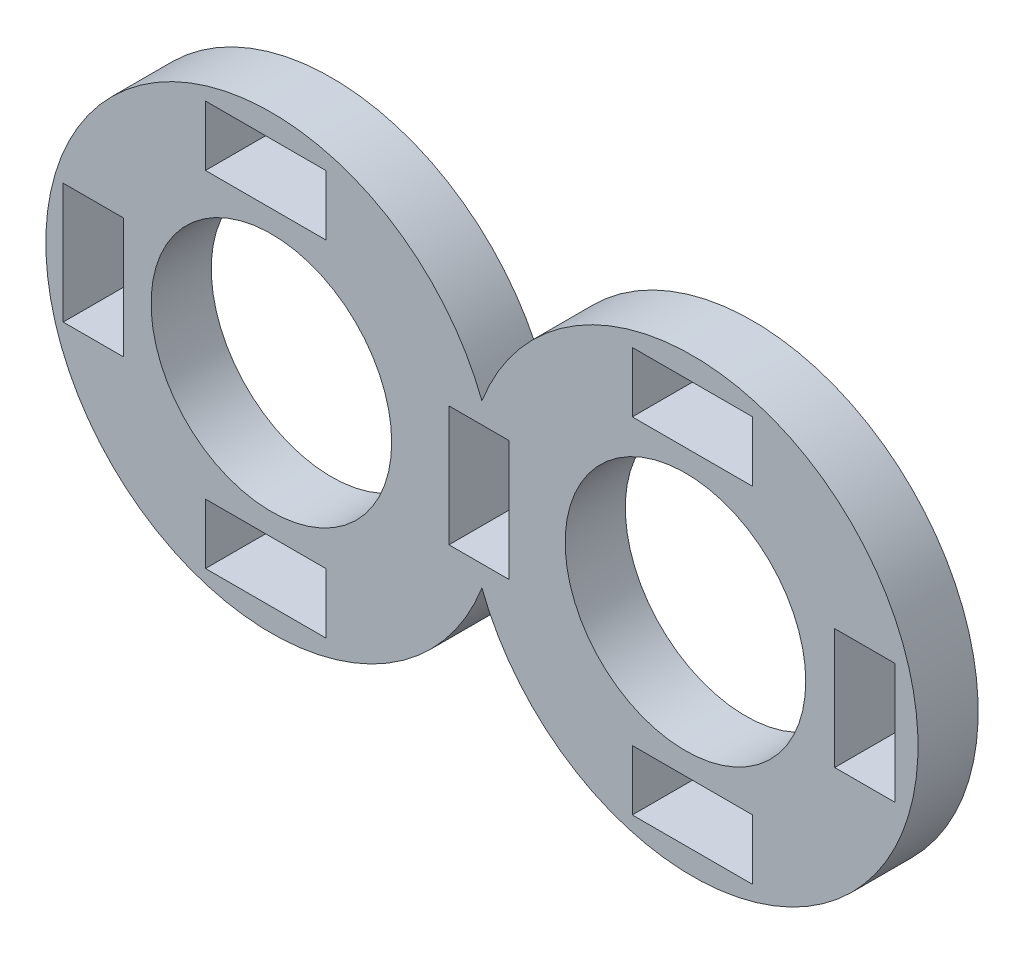
SolidWorks part; units mm, degrees
ref_plane "Front Plane" through (0, 0, 0) normal (0, 0, 1) x (1, 0, 0)
ref_plane "Top Plane" through (0, 0, 0) normal (0, 1, 0) x (1, 0, 0)
ref_plane "Right Plane" through (0, 0, 0) normal (1, 0, 0) x (0, 0, -1)
sketch "Sketch1" plane through (0, 0, 0) normal (0, 0, 1) x (1, 0, 0)
  line L0 (7, 0) -> (0, 0) construction
  circle A0 centre (0, 0) radius 3.75
  circle A1 centre (7, 0) radius 3.75
  circle A2 centre (0, 0) radius 2
  circle A3 centre (7, 0) radius 2
extrude "Boss-Extrude1" add sketch "Sketch1" along normal blind 1 contours A0 | A1
sketch "Sketch2" plane through (0, 0, 0) normal (0, 0, 1) x (1, 0, 0)
  circle A0 centre (0, 0) radius 2
  circle A1 centre (6.8835, 0) radius 2
  point P4 (0, 0)
extrude "Cut-Extrude3" cut sketch "Sketch2" along normal blind 1 from surface starting at face at (3.5, 0, 0)
sketch "Sketch3" plane through (0, 0, 0) normal (0, 0, 1) x (1, 0, 0)
  line L5 (6, -2.3653) -> (8, -2.3653)
  line L6 (9.3653, -1) -> (10.3653, -1)
  line L7 (9.3653, -1) -> (9.3653, 1)
  line L8 (9.3653, 1) -> (10.3653, 1)
  line L9 (10.3653, -1) -> (10.3653, 1)
  line L12 (6, -2.3653) -> (6, -3.3653)
  line L13 (6, -3.3653) -> (8, -3.3653)
  line L14 (8, -2.3653) -> (8, -3.3653)
  line L15 (8, 2.3653) -> (6, 2.3653)
  line L16 (8, 2.3653) -> (8, 3.3653)
  line L17 (8, 3.3653) -> (6, 3.3653)
  line L18 (6, 2.3653) -> (6, 3.3653)
  line L20 (0.9046, -2.3653) -> (0.9046, -3.3653)
  line L21 (0.9046, -3.3653) -> (-1.0954, -3.3653)
  line L22 (-1.0954, -2.3653) -> (-1.0954, -3.3653)
  line L23 (0.9046, -2.3653) -> (-1.0954, -2.3653)
  line L24 (0.9046, 2.3653) -> (0.9046, 3.3653)
  line L25 (-1.0954, 3.3653) -> (0.9046, 3.3653)
  line L26 (-1.0954, 2.3653) -> (-1.0954, 3.3653)
  line L27 (-1.0954, 2.3653) -> (0.9046, 2.3653)
  line L28 (-2.4607, -1) -> (-3.4607, -1)
  line L29 (-2.4607, -1) -> (-2.4607, 1)
  line L30 (-2.4607, 1) -> (-3.4607, 1)
  line L31 (-3.4607, -1) -> (-3.4607, 1)
  line L33 (3.9523, -1) -> (2.9523, -1)
  line L34 (3.9523, -1) -> (3.9523, 1)
  line L35 (3.9523, 1) -> (2.9523, 1)
  line L36 (2.9523, -1) -> (2.9523, 1)
  dimension "D3" = 2
  dimension "D4" = 2
extrude "Cut-Extrude4" cut sketch "Sketch3" along normal blind 1 from surface starting at face at (2, 0, 0)
